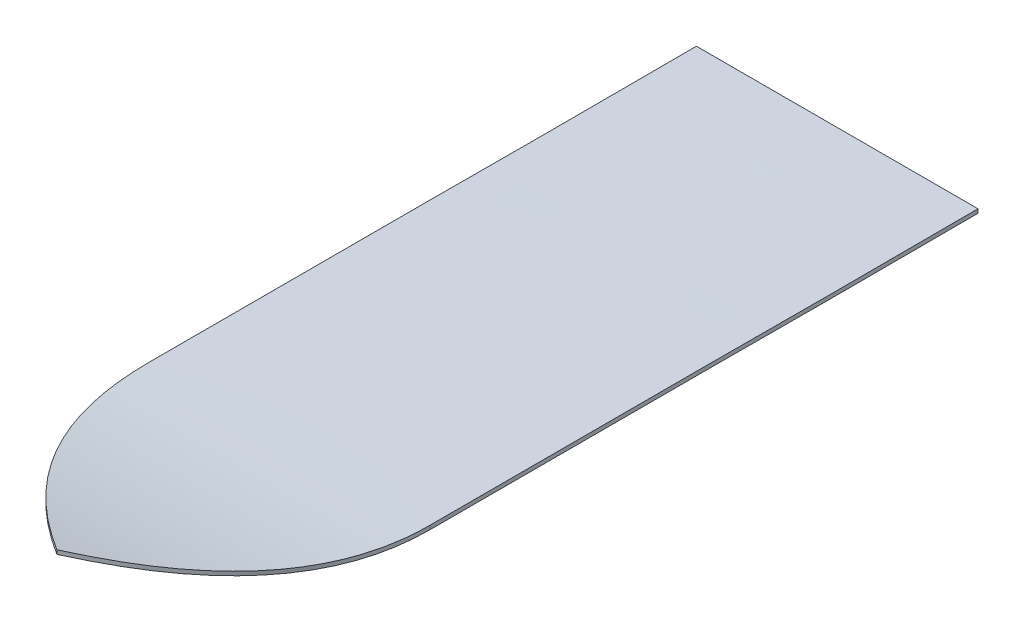
SolidWorks part; units mm, degrees
ref_plane "Front Plane" through (0, 0, 0) normal (0, 0, 1) x (1, 0, 0)
ref_plane "Top Plane" through (0, 0, 0) normal (0, 1, 0) x (1, 0, 0)
ref_plane "Right Plane" through (0, 0, 0) normal (1, 0, 0) x (0, 0, -1)
sketch "Sketch1" plane through (0, 0, 0) normal (1, 0, 0) x (0, 0, -1)
  line L8 (-1314.6699, -205.1873) -> (-1320.1211, -229.5857)
  line L13 (3673.2128, -361.3848) -> (3673.2382, -386.3848)
  spline S0 degree 3 poles (-1314.6699, -205.1873) (-1248.304, -220.0151) (-1111.6667, -250.3556) (-921.8868, -282.8852) (-748.92, -307.4255) (-597.9895, -324.9979) (-444.4622, -339.2072) (-281.8114, -350.4776) (-109.6483, -358.3054) (21.8625, -361.0829) (103.6493, -361.6821) (127.5759, -361.7636) (144.7009, -361.777) (165.2681, -361.7707) (264.6625, -361.7584) (442.8877, -361.7352) (717.0817, -361.6979) (1018.695, -361.6569) (1347.7277, -361.6121) (1711.0346, -361.5627) (1985.2284, -361.5227) (2158.3135, -361.5049) (2189.1592, -361.5133) (2201.157, -361.4871) (2209.7174, -361.589) (2230.2026, -361.7628) (2299.6545, -362.3395) (2415.1982, -363.07) (2539.4678, -363.4947) (2639.2883, -363.6434) (2713.2568, -363.667) (2786.5034, -363.6144) (2859.2038, -363.4976) (2931.5321, -363.3284) (3003.6676, -363.119) (3075.77, -362.8803) (3208.3258, -362.4163) (3402.0724, -361.6602) (3582.8327, -361.4766) (3673.2128, -361.3848) knots 0.002527 0.002527 0.002527 0.002527 0.046875 0.09375 0.125 0.15625 0.1875 0.21875 0.253906 0.289062 0.294922 0.300781 0.302734 0.304688 0.3125 0.359375 0.40625 0.46875 0.53125 0.59375 0.675781 0.6875 0.692383 0.693359 0.694336 0.697266 0.705078 0.734375 0.765625 0.78125 0.796875 0.8125 0.828125 0.84375 0.859375 0.875 0.890625 0.945312 1 1 1 1
  spline S1 degree 1 poles (-1320.1211, -229.5857) (3673.2382, -386.3848) knots 0 0 1 1 construction
  spline S2 degree 3 poles (-1320.1211, -229.5857) (-1308.4473, -232.194) (-1285.1133, -237.4018) (-1238.3071, -247.7556) (-1179.5332, -260.4566) (-1108.23, -274.9483) (-1036.0934, -288.3519) (-963.2745, -300.7919) (-865.3724, -316.2266) (-741.4835, -333.5844) (-590.1438, -350.9423) (-436.2554, -364.9439) (-279.7708, -375.5561) (-147.2179, -381.5847) (-39.8824, -384.7177) (27.7384, -385.9724) (82.1623, -386.5532) (116.3019, -386.7419) (143.7219, -386.7816) (171.0827, -386.7669) (205.2626, -386.7669) (246.2898, -386.7603) (300.9889, -386.7538) (396.7144, -386.7411) (533.4645, -386.7229) (697.5652, -386.7005) (861.6658, -386.6782) (1025.7663, -386.6559) (1189.8669, -386.6336) (1353.9675, -386.6113) (1518.0681, -386.589) (1682.1688, -386.5663) (1818.9192, -386.5468) (1928.3194, -386.532) (1996.6945, -386.5232) (2051.3946, -386.5166) (2092.4194, -386.512) (2126.6073, -386.5078) (2150.5351, -386.5072) (2164.2081, -386.5081) (2174.4601, -386.51) (2183.0179, -386.5106) (2189.8734, -386.5062) (2194.161, -386.5013) (2197.5955, -386.4944) (2200.0664, -386.4929) (2202.4424, -386.5061) (2204.94, -386.5331) (2207.5302, -386.5621) (2210.9608, -386.5969) (2216.954, -386.6522) (2225.4518, -386.7227) (2239.0156, -386.8367) (2262.6554, -387.0303) (2296.1589, -387.2857) (2349.204, -387.6464) (2414.5218, -388.0133) (2491.4925, -388.3309) (2567.2266, -388.5377) (2666.7883, -388.6816) (2789.0148, -388.6434) (2933.5265, -388.3437) (3053.2764, -387.9595) (3149.4425, -387.6224) (3245.8244, -387.2679) (3343.1767, -386.9268) (3442.9931, -386.6861) (3519.0952, -386.5585) (3583.1551, -386.4791) (3634.601, -386.424) (3660.3624, -386.3978) (3673.2382, -386.3848) knots 0.002527 0.002527 0.002527 0.002527 0.01032 0.018113 0.033698 0.049284 0.064869 0.080455 0.09604 0.127211 0.158382 0.189553 0.220724 0.251895 0.267481 0.283066 0.290859 0.298652 0.302548 0.306445 0.314237 0.32203 0.329823 0.345408 0.376579 0.407751 0.438922 0.470093 0.501264 0.532435 0.563606 0.594777 0.625948 0.641533 0.657119 0.664911 0.672704 0.680497 0.684393 0.686342 0.68829 0.690238 0.691212 0.692186 0.692673 0.69316 0.693647 0.694134 0.694621 0.695108 0.696083 0.698031 0.699979 0.703875 0.711668 0.719461 0.735046 0.750632 0.766217 0.781803 0.812974 0.844145 0.875316 0.890901 0.906487 0.937658 0.953243 0.968829 0.984414 0.992207 1 1 1 1
  dimension "D1" = 25
extrude "Boss-Extrude1" add sketch "Sketch1" along normal blind 1524 and the other way blind 1524
sketch "Sketch3" plane through (0, 0, 0) normal (0, 1, 0) x (1, 0, 0)
  line L0 (-900, 3691.0273) -> (900, 3691.0273)
  line L1 (-900, 3691.0273) -> (-900, 173.4936)
  line L2 (900, 3691.0273) -> (900, 173.4936)
  line L3 (0, 2955.5244) -> (0, -2061.9995) construction
  line L4 (-2883.7113, 6367.4108) -> (2847.7461, 6367.4108)
  line L5 (-2883.7113, 6367.4108) -> (-2883.7113, -1635.8951)
  line L6 (-2883.7113, -1635.8951) -> (2847.7461, -1635.8951)
  line L7 (2847.7461, 6367.4108) -> (2847.7461, -1635.8951)
  line L8 (-94.9374, 0) -> (0, 0) construction
  line L11 (-1524, 1954.9582) -> (1524, 1954.9582) construction
  spline S0 degree 2 poles (-900, 173.4936) (-900, -701.145) (0, -1314.6699) knots 0 0 0 1 1 1
  spline S1 degree 2 poles (900, 173.4936) (900, -701.145) (0, -1314.6699) knots 0 0 0 1 1 1
  dimension "D1" = 1800
extrude "Cut-Extrude1" cut sketch "Sketch3" against normal through all both and the other way through all
